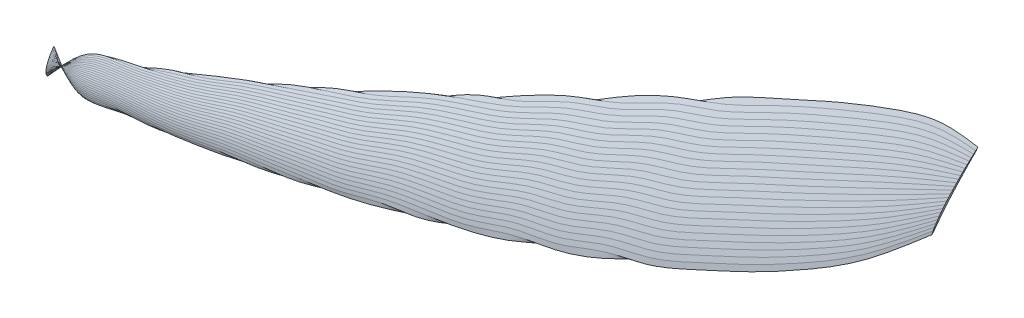
SolidWorks part; units mm, degrees
ref_plane "Front Plane" through (0, 0, 0) normal (0, 0, 1) x (1, 0, 0)
ref_plane "Top Plane" through (0, 0, 0) normal (0, 1, 0) x (1, 0, 0)
ref_plane "Right Plane" through (0, 0, 0) normal (1, 0, 0) x (0, 0, -1)
ref_plane "Plane1" through (560, 0, 0) normal (1, 0, 0) x (0, 0, -1)
sketch "Sketch1" plane through (560, 0, 0) normal (1, 0, 0) x (0, 0, -1)
  line L0 (6.3361, 23.506) -> (5.0614, 21.8132)
  line L1 (5.0614, 21.8132) -> (3.8256, 20.0917)
  line L2 (3.8256, 20.0917) -> (2.6281, 18.3434)
  line L3 (2.6281, 18.3434) -> (1.4689, 16.5695)
  line L4 (1.4689, 16.5695) -> (0.3482, 14.771)
  line L5 (0.3482, 14.771) -> (-0.734, 12.9491)
  line L6 (-0.734, 12.9491) -> (-1.777, 11.1045)
  line L7 (-1.777, 11.1045) -> (-2.7798, 9.2376)
  line L8 (-2.7798, 9.2376) -> (-3.7409, 7.3491)
  line L9 (-3.7409, 7.3491) -> (-4.6589, 5.4391)
  line L10 (-4.6589, 5.4391) -> (-5.5297, 3.5072)
  line L11 (-5.5297, 3.5072) -> (-6.3519, 1.5542)
  line L12 (-6.3519, 1.5542) -> (-7.1221, -0.4199)
  line L13 (-7.1221, -0.4199) -> (-7.8343, -2.4157)
  line L14 (-7.8343, -2.4157) -> (-8.4715, -4.4366)
  line L15 (-8.4715, -4.4366) -> (-9.0121, -6.4853)
  line L16 (-9.0121, -6.4853) -> (-9.447, -8.5591)
  line L17 (-9.447, -8.5591) -> (-9.7657, -10.6538)
  line L18 (-9.7657, -10.6538) -> (-9.9549, -12.7641)
  line L19 (-9.9549, -12.7641) -> (-9.9984, -14.8823)
  line L20 (-9.9984, -14.8823) -> (-9.8732, -16.9969)
  line L21 (-9.8732, -16.9969) -> (-9.5349, -19.0876)
  line L22 (-9.5349, -19.0876) -> (-8.9029, -21.1071)
  line L23 (-8.9029, -21.1071) -> (-7.7612, -22.8741)
  line L24 (-7.7612, -22.8741) -> (-5.8142, -23.3089)
  line L25 (-5.8142, -23.3089) -> (-4.3081, -21.8645)
  line L26 (-4.3081, -21.8645) -> (-3.3614, -19.9721)
  line L27 (-3.3614, -19.9721) -> (-2.659, -17.9734)
  line L28 (-2.659, -17.9734) -> (-2.0869, -15.9332)
  line L29 (-2.0869, -15.9332) -> (-1.5892, -13.8734)
  line L30 (-1.5892, -13.8734) -> (-1.1344, -11.8036)
  line L31 (-1.1344, -11.8036) -> (-0.7002, -9.7295)
  line L32 (-0.7002, -9.7295) -> (-0.2712, -7.6542)
  line L33 (-0.2712, -7.6542) -> (0.1651, -5.5805)
  line L34 (0.1651, -5.5805) -> (0.6108, -3.5087)
  line L35 (0.6108, -3.5087) -> (1.0479, -1.4352)
  line L36 (1.0479, -1.4352) -> (1.4801, 0.6394)
  line L37 (1.4801, 0.6394) -> (1.9114, 2.7142)
  line L38 (1.9114, 2.7142) -> (2.3454, 4.7884)
  line L39 (2.3454, 4.7884) -> (2.7846, 6.8616)
  line L40 (2.7846, 6.8616) -> (3.2309, 8.9331)
  line L41 (3.2309, 8.9331) -> (3.6858, 11.0029)
  line L42 (3.6858, 11.0029) -> (4.1498, 13.0706)
  line L43 (4.1498, 13.0706) -> (4.623, 15.1362)
  line L44 (4.623, 15.1362) -> (5.1055, 17.1997)
  line L45 (5.1055, 17.1997) -> (5.5963, 19.2612)
  line L46 (5.5963, 19.2612) -> (6.0946, 21.3209)
  line L47 (6.0946, 21.3209) -> (6.3361, 23.506)
ref_plane "Plane2" through (618.1875, 0, 0) normal (1, 0, 0) x (0, 0, -1)
sketch "Sketch2" plane through (618.1875, 0, 0) normal (1, 0, 0) x (0, 0, -1)
  line L0 (21.3816, 31.2165) -> (19.6626, 28.9786)
  line L1 (19.6626, 28.9786) -> (17.993, 26.7036)
  line L2 (17.993, 26.7036) -> (16.372, 24.3938)
  line L3 (16.372, 24.3938) -> (14.7997, 22.0505)
  line L4 (14.7997, 22.0505) -> (13.2762, 19.6752)
  line L5 (13.2762, 19.6752) -> (11.8016, 17.2692)
  line L6 (11.8016, 17.2692) -> (10.3769, 14.8334)
  line L7 (10.3769, 14.8334) -> (9.0032, 12.3684)
  line L8 (9.0032, 12.3684) -> (7.6822, 9.8748)
  line L9 (7.6822, 9.8748) -> (6.4163, 7.3528)
  line L10 (6.4163, 7.3528) -> (5.2096, 4.8019)
  line L11 (5.2096, 4.8019) -> (4.064, 2.2231)
  line L12 (4.064, 2.2231) -> (2.9836, -0.3838)
  line L13 (2.9836, -0.3838) -> (1.9767, -3.0199)
  line L14 (1.9767, -3.0199) -> (1.062, -5.6892)
  line L15 (1.062, -5.6892) -> (0.2698, -8.3974)
  line L16 (0.2698, -8.3974) -> (-0.3882, -11.1412)
  line L17 (-0.3882, -11.1412) -> (-0.8983, -13.9163)
  line L18 (-0.8983, -13.9163) -> (-1.2464, -16.7163)
  line L19 (-1.2464, -16.7163) -> (-1.4104, -19.5329)
  line L20 (-1.4104, -19.5329) -> (-1.3641, -22.3536)
  line L21 (-1.3641, -22.3536) -> (-1.0503, -25.1566)
  line L22 (-1.0503, -25.1566) -> (-0.3671, -27.891)
  line L23 (-0.3671, -27.891) -> (0.9874, -30.3437)
  line L24 (0.9874, -30.3437) -> (3.5302, -30.8718)
  line L25 (3.5302, -30.8718) -> (5.3879, -28.7926)
  line L26 (5.3879, -28.7926) -> (6.5789, -26.2374)
  line L27 (6.5789, -26.2374) -> (7.4965, -23.5694)
  line L28 (7.4965, -23.5694) -> (8.2758, -20.8574)
  line L29 (8.2758, -20.8574) -> (8.9785, -18.1244)
  line L30 (8.9785, -18.1244) -> (9.6413, -15.3814)
  line L31 (9.6413, -15.3814) -> (10.2893, -12.6348)
  line L32 (10.2893, -12.6348) -> (10.9409, -9.8891)
  line L33 (10.9409, -9.8891) -> (11.6102, -7.1477)
  line L34 (11.6102, -7.1477) -> (12.2955, -4.4102)
  line L35 (12.2955, -4.4102) -> (12.9735, -1.6709)
  line L36 (12.9735, -1.6709) -> (13.6491, 1.069)
  line L37 (13.6491, 1.069) -> (14.3273, 3.8082)
  line L38 (14.3273, 3.8082) -> (15.012, 6.5458)
  line L39 (15.012, 6.5458) -> (15.7062, 9.2811)
  line L40 (15.7062, 9.2811) -> (16.4121, 12.0133)
  line L41 (16.4121, 12.0133) -> (17.1313, 14.7421)
  line L42 (17.1313, 14.7421) -> (17.8645, 17.4671)
  line L43 (17.8645, 17.4671) -> (18.6117, 20.1884)
  line L44 (18.6117, 20.1884) -> (19.3729, 22.9057)
  line L45 (19.3729, 22.9057) -> (20.147, 25.6194)
  line L46 (20.147, 25.6194) -> (20.9328, 28.3297)
  line L47 (20.9328, 28.3297) -> (21.3816, 31.2165)
ref_plane "Plane3" through (676.375, 0, 0) normal (1, 0, 0) x (0, 0, -1)
sketch "Sketch3" plane through (676.375, 0, 0) normal (1, 0, 0) x (0, 0, -1)
  line L0 (39.403, 37.0958) -> (37.3256, 34.4466)
  line L1 (37.3256, 34.4466) -> (35.3042, 31.7544)
  line L2 (35.3042, 31.7544) -> (33.338, 29.0216)
  line L3 (33.338, 29.0216) -> (31.4273, 26.2498)
  line L4 (31.4273, 26.2498) -> (29.5721, 23.4405)
  line L5 (29.5721, 23.4405) -> (27.7727, 20.5951)
  line L6 (27.7727, 20.5951) -> (26.03, 17.7146)
  line L7 (26.03, 17.7146) -> (24.3455, 14.7998)
  line L8 (24.3455, 14.7998) -> (22.7207, 11.8512)
  line L9 (22.7207, 11.8512) -> (21.1588, 8.8689)
  line L10 (21.1588, 8.8689) -> (19.6636, 5.8526)
  line L11 (19.6636, 5.8526) -> (18.2372, 2.8031)
  line L12 (18.2372, 2.8031) -> (16.8846, -0.2798)
  line L13 (16.8846, -0.2798) -> (15.6143, -3.3975)
  line L14 (15.6143, -3.3975) -> (14.4464, -6.5548)
  line L15 (14.4464, -6.5548) -> (13.4177, -9.7601)
  line L16 (13.4177, -9.7601) -> (12.5427, -13.0107)
  line L17 (12.5427, -13.0107) -> (11.8349, -16.3017)
  line L18 (11.8349, -16.3017) -> (11.3086, -19.6265)
  line L19 (11.3086, -19.6265) -> (10.991, -22.9775)
  line L20 (10.991, -22.9775) -> (10.9083, -26.3423)
  line L21 (10.9083, -26.3423) -> (11.1251, -29.7006)
  line L22 (11.1251, -29.7006) -> (11.7565, -33.0038)
  line L23 (11.7565, -33.0038) -> (13.1712, -36.0333)
  line L24 (13.1712, -36.0333) -> (16.1307, -36.5557)
  line L25 (16.1307, -36.5557) -> (18.1767, -33.9182)
  line L26 (18.1767, -33.9182) -> (19.5316, -30.8386)
  line L27 (19.5316, -30.8386) -> (20.6226, -27.6542)
  line L28 (20.6226, -27.6542) -> (21.5811, -24.4269)
  line L29 (21.5811, -24.4269) -> (22.4714, -21.1801)
  line L30 (22.4714, -21.1801) -> (23.3324, -17.9255)
  line L31 (23.3324, -17.9255) -> (24.1895, -14.6697)
  line L32 (24.1895, -14.6697) -> (25.0615, -11.418)
  line L33 (25.0615, -11.418) -> (25.9631, -8.1743)
  line L34 (25.9631, -8.1743) -> (26.8866, -4.9368)
  line L35 (26.8866, -4.9368) -> (27.8065, -1.6982)
  line L36 (27.8065, -1.6982) -> (28.7282, 1.5398)
  line L37 (28.7282, 1.5398) -> (29.6568, 4.7759)
  line L38 (29.6568, 4.7759) -> (30.5964, 8.0088)
  line L39 (30.5964, 8.0088) -> (31.55, 11.2375)
  line L40 (31.55, 11.2375) -> (32.5201, 14.4614)
  line L41 (32.5201, 14.4614) -> (33.508, 17.6798)
  line L42 (33.508, 17.6798) -> (34.5146, 20.8925)
  line L43 (34.5146, 20.8925) -> (35.5398, 24.0993)
  line L44 (35.5398, 24.0993) -> (36.5836, 27.3)
  line L45 (36.5836, 27.3) -> (37.6447, 30.4951)
  line L46 (37.6447, 30.4951) -> (38.7218, 33.6848)
  line L47 (38.7218, 33.6848) -> (39.403, 37.0958)
ref_plane "Plane4" through (734.5625, 0, 0) normal (1, 0, 0) x (0, 0, -1)
sketch "Sketch4" plane through (734.5625, 0, 0) normal (1, 0, 0) x (0, 0, -1)
  line L0 (60.5598, 42.9415) -> (58.1177, 39.8798)
  line L1 (58.1177, 39.8798) -> (55.7372, 36.7699)
  line L2 (55.7372, 36.7699) -> (53.4174, 33.6144)
  line L3 (53.4174, 33.6144) -> (51.1589, 30.4148)
  line L4 (51.1589, 30.4148) -> (48.9615, 27.173)
  line L5 (48.9615, 27.173) -> (46.8257, 23.8902)
  line L6 (46.8257, 23.8902) -> (44.7523, 20.5676)
  line L7 (44.7523, 20.5676) -> (42.743, 17.206)
  line L8 (42.743, 17.206) -> (40.7994, 13.8059)
  line L9 (40.7994, 13.8059) -> (38.9251, 10.3671)
  line L10 (38.9251, 10.3671) -> (37.1235, 6.8897)
  line L11 (37.1235, 6.8897) -> (35.3971, 3.3744)
  line L12 (35.3971, 3.3744) -> (33.7517, -0.1795)
  line L13 (33.7517, -0.1795) -> (32.1952, -3.7733)
  line L14 (32.1952, -3.7733) -> (30.7491, -7.4127)
  line L15 (30.7491, -7.4127) -> (29.4561, -11.1092)
  line L16 (29.4561, -11.1092) -> (28.3334, -14.861)
  line L17 (28.3334, -14.861) -> (27.3933, -18.6625)
  line L18 (27.3933, -18.6625) -> (26.652, -22.5077)
  line L19 (26.652, -22.5077) -> (26.1376, -26.3895)
  line L20 (26.1376, -26.3895) -> (25.8803, -30.2967)
  line L21 (25.8803, -30.2967) -> (25.9467, -34.2111)
  line L22 (25.9467, -34.2111) -> (26.4661, -38.0894)
  line L23 (26.4661, -38.0894) -> (27.8743, -41.716)
  line L24 (27.8743, -41.716) -> (31.2137, -42.1175)
  line L25 (31.2137, -42.1175) -> (33.4163, -38.9059)
  line L26 (33.4163, -38.9059) -> (34.9516, -35.3049)
  line L27 (34.9516, -35.3049) -> (36.2355, -31.6052)
  line L28 (36.2355, -31.6052) -> (37.4011, -27.8662)
  line L29 (37.4011, -27.8662) -> (38.5109, -24.1103)
  line L30 (38.5109, -24.1103) -> (39.6023, -20.349)
  line L31 (39.6023, -20.349) -> (40.7017, -16.59)
  line L32 (40.7017, -16.59) -> (41.8278, -12.8389)
  line L33 (41.8278, -12.8389) -> (42.995, -9.1005)
  line L34 (42.995, -9.1005) -> (44.1892, -5.3705)
  line L35 (44.1892, -5.3705) -> (45.384, -1.6407)
  line L36 (45.384, -1.6407) -> (46.5848, 2.0871)
  line L37 (46.5848, 2.0871) -> (47.7971, 5.8112)
  line L38 (47.7971, 5.8112) -> (49.0249, 9.5303)
  line L39 (49.0249, 9.5303) -> (50.2711, 13.2432)
  line L40 (50.2711, 13.2432) -> (51.5383, 16.949)
  line L41 (51.5383, 16.949) -> (52.8278, 20.6471)
  line L42 (52.8278, 20.6471) -> (54.1404, 24.337)
  line L43 (54.1404, 24.337) -> (55.4759, 28.0188)
  line L44 (55.4759, 28.0188) -> (56.8343, 31.6921)
  line L45 (56.8343, 31.6921) -> (58.2143, 35.3574)
  line L46 (58.2143, 35.3574) -> (59.6142, 39.0151)
  line L47 (59.6142, 39.0151) -> (60.5598, 42.9415)
ref_plane "Plane5" through (792.75, 0, 0) normal (1, 0, 0) x (0, 0, -1)
sketch "Sketch5" plane through (792.75, 0, 0) normal (1, 0, 0) x (0, 0, -1)
  line L0 (84.7982, 49.1414) -> (81.961, 45.6375)
  line L1 (81.961, 45.6375) -> (79.1907, 42.0805)
  line L2 (79.1907, 42.0805) -> (76.4862, 38.4732)
  line L3 (76.4862, 38.4732) -> (73.8483, 34.8169)
  line L4 (73.8483, 34.8169) -> (71.2765, 31.1138)
  line L5 (71.2765, 31.1138) -> (68.7718, 27.365)
  line L6 (68.7718, 27.365) -> (66.3347, 23.5719)
  line L7 (66.3347, 23.5719) -> (63.967, 19.7352)
  line L8 (63.967, 19.7352) -> (61.6704, 15.8554)
  line L9 (61.6704, 15.8554) -> (59.449, 11.9321)
  line L10 (59.449, 11.9321) -> (57.3057, 7.9656)
  line L11 (57.3057, 7.9656) -> (55.2433, 3.9565)
  line L12 (55.2433, 3.9565) -> (53.2683, -0.0964)
  line L13 (53.2683, -0.0964) -> (51.3881, -4.1941)
  line L14 (51.3881, -4.1941) -> (49.6251, -8.3434)
  line L15 (49.6251, -8.3434) -> (48.0277, -12.5592)
  line L16 (48.0277, -12.5592) -> (46.6159, -16.8407)
  line L17 (46.6159, -16.8407) -> (45.4005, -21.1819)
  line L18 (45.4005, -21.1819) -> (44.3994, -25.5775)
  line L19 (44.3994, -25.5775) -> (43.6416, -30.0213)
  line L20 (43.6416, -30.0213) -> (43.1604, -34.5032)
  line L21 (43.1604, -34.5032) -> (43.0249, -39.0084)
  line L22 (43.0249, -39.0084) -> (43.3769, -43.4996)
  line L23 (43.3769, -43.4996) -> (44.7206, -47.7733)
  line L24 (44.7206, -47.7733) -> (48.4276, -47.9326)
  line L25 (48.4276, -47.9326) -> (50.8033, -44.1197)
  line L26 (50.8033, -44.1197) -> (52.5527, -39.9658)
  line L27 (52.5527, -39.9658) -> (54.0719, -35.7211)
  line L28 (54.0719, -35.7211) -> (55.4855, -31.4399)
  line L29 (55.4855, -31.4399) -> (56.8566, -27.1448)
  line L30 (56.8566, -27.1448) -> (58.2222, -22.848)
  line L31 (58.2222, -22.848) -> (59.6076, -18.5575)
  line L32 (59.6076, -18.5575) -> (61.0315, -14.2797)
  line L33 (61.0315, -14.2797) -> (62.508, -10.0198)
  line L34 (62.508, -10.0198) -> (64.0161, -5.7708)
  line L35 (64.0161, -5.7708) -> (65.5289, -1.5236)
  line L36 (65.5289, -1.5236) -> (67.0522, 2.7199)
  line L37 (67.0522, 2.7199) -> (68.5917, 6.9575)
  line L38 (68.5917, 6.9575) -> (70.1511, 11.1879)
  line L39 (70.1511, 11.1879) -> (71.7334, 15.4097)
  line L40 (71.7334, 15.4097) -> (73.341, 19.6219)
  line L41 (73.341, 19.6219) -> (74.9753, 23.8239)
  line L42 (74.9753, 23.8239) -> (76.637, 28.0151)
  line L43 (76.637, 28.0151) -> (78.3259, 32.1954)
  line L44 (78.3259, 32.1954) -> (80.0419, 36.3647)
  line L45 (80.0419, 36.3647) -> (81.7836, 40.5233)
  line L46 (81.7836, 40.5233) -> (83.5493, 44.6718)
  line L47 (83.5493, 44.6718) -> (84.7982, 49.1414)
ref_plane "Plane6" through (850.9375, 0, 0) normal (1, 0, 0) x (0, 0, -1)
sketch "Sketch6" plane through (850.9375, 0, 0) normal (1, 0, 0) x (0, 0, -1)
  line L0 (111.9093, 55.4384) -> (108.6555, 51.483)
  line L1 (108.6555, 51.483) -> (105.4732, 47.4699)
  line L2 (105.4732, 47.4699) -> (102.3613, 43.402)
  line L3 (102.3613, 43.402) -> (99.3207, 39.2804)
  line L4 (99.3207, 39.2804) -> (96.3509, 35.1076)
  line L5 (96.3509, 35.1076) -> (93.4528, 30.8846)
  line L6 (93.4528, 30.8846) -> (90.6272, 26.6129)
  line L7 (90.6272, 26.6129) -> (87.8756, 22.293)
  line L8 (87.8756, 22.293) -> (85.2, 17.9258)
  line L9 (85.2, 17.9258) -> (82.6048, 13.5102)
  line L10 (82.6048, 13.5102) -> (80.0923, 9.0471)
  line L11 (80.0923, 9.0471) -> (77.6657, 4.5367)
  line L12 (77.6657, 4.5367) -> (75.332, -0.0224)
  line L13 (75.332, -0.0224) -> (73.0979, -4.6312)
  line L14 (73.0979, -4.6312) -> (70.9869, -9.2973)
  line L15 (70.9869, -9.2973) -> (69.0528, -14.0396)
  line L16 (69.0528, -14.0396) -> (67.3172, -18.858)
  line L17 (67.3172, -18.858) -> (65.7902, -23.7464)
  line L18 (65.7902, -23.7464) -> (64.491, -28.7001)
  line L19 (64.491, -28.7001) -> (63.4488, -33.7141)
  line L20 (63.4488, -33.7141) -> (62.6993, -38.7798)
  line L21 (62.6993, -38.7798) -> (62.3132, -43.8857)
  line L22 (62.3132, -43.8857) -> (62.4417, -49.0023)
  line L23 (62.4417, -49.0023) -> (63.6555, -53.9454)
  line L24 (63.6555, -53.9454) -> (67.688, -53.7533)
  line L25 (67.688, -53.7533) -> (70.2552, -49.3348)
  line L26 (70.2552, -49.3348) -> (72.2442, -44.6159)
  line L27 (72.2442, -44.6159) -> (74.0262, -39.8143)
  line L28 (74.0262, -39.8143) -> (75.7213, -34.9811)
  line L29 (75.7213, -34.9811) -> (77.3881, -30.1381)
  line L30 (77.3881, -30.1381) -> (79.0628, -25.2978)
  line L31 (79.0628, -25.2978) -> (80.7701, -20.469)
  line L32 (80.7701, -20.469) -> (82.5285, -15.6585)
  line L33 (82.5285, -15.6585) -> (84.3514, -10.8721)
  line L34 (84.3514, -10.8721) -> (86.2103, -6.0996)
  line L35 (86.2103, -6.0996) -> (88.0788, -1.3307)
  line L36 (88.0788, -1.3307) -> (89.9626, 3.432)
  line L37 (89.9626, 3.432) -> (91.8674, 8.1865)
  line L38 (91.8674, 8.1865) -> (93.797, 12.9309)
  line L39 (93.797, 12.9309) -> (95.7541, 17.664)
  line L40 (95.7541, 17.664) -> (97.741, 22.3847)
  line L41 (97.741, 22.3847) -> (99.7592, 27.0921)
  line L42 (99.7592, 27.0921) -> (101.8092, 31.7858)
  line L43 (101.8092, 31.7858) -> (103.8908, 36.4655)
  line L44 (103.8908, 36.4655) -> (106.0038, 41.1311)
  line L45 (106.0038, 41.1311) -> (108.1468, 45.7831)
  line L46 (108.1468, 45.7831) -> (110.3179, 50.4219)
  line L47 (110.3179, 50.4219) -> (111.9093, 55.4384)
ref_plane "Plane7" through (909.125, 0, 0) normal (1, 0, 0) x (0, 0, -1)
sketch "Sketch7" plane through (909.125, 0, 0) normal (1, 0, 0) x (0, 0, -1)
  line L0 (141.8104, 61.8077) -> (138.1179, 57.3929)
  line L1 (138.1179, 57.3929) -> (134.5011, 52.916)
  line L2 (134.5011, 52.916) -> (130.9586, 48.3799)
  line L3 (130.9586, 48.3799) -> (127.4916, 43.7858)
  line L4 (127.4916, 43.7858) -> (124.0995, 39.1363)
  line L5 (124.0995, 39.1363) -> (120.7834, 34.4322)
  line L6 (120.7834, 34.4322) -> (117.5439, 29.675)
  line L7 (117.5439, 29.675) -> (114.3826, 24.8655)
  line L8 (114.3826, 24.8655) -> (111.3015, 20.0043)
  line L9 (111.3015, 20.0043) -> (108.3054, 15.0902)
  line L10 (108.3054, 15.0902) -> (105.3961, 10.1242)
  line L11 (105.3961, 10.1242) -> (102.5768, 5.1066)
  line L12 (102.5768, 5.1066) -> (99.8553, 0.0354)
  line L13 (99.8553, 0.0354) -> (97.2372, -5.0901)
  line L14 (97.2372, -5.0901) -> (94.7468, -10.2785)
  line L15 (94.7468, -10.2785) -> (92.444, -15.5529)
  line L16 (92.444, -15.5529) -> (90.3498, -20.9135)
  line L17 (90.3498, -20.9135) -> (88.4751, -26.3546)
  line L18 (88.4751, -26.3546) -> (86.8395, -31.8722)
  line L19 (86.8395, -31.8722) -> (85.4723, -37.4623)
  line L20 (85.4723, -37.4623) -> (84.4108, -43.1182)
  line L21 (84.4108, -43.1182) -> (83.726, -48.8314)
  line L22 (83.726, -48.8314) -> (83.5754, -54.5815)
  line L23 (83.5754, -54.5815) -> (84.5911, -60.2113)
  line L24 (84.5911, -60.2113) -> (88.9125, -59.5634)
  line L25 (88.9125, -59.5634) -> (91.692, -54.5332)
  line L26 (91.692, -54.5332) -> (93.9519, -49.2407)
  line L27 (93.9519, -49.2407) -> (96.0304, -43.8737)
  line L28 (96.0304, -43.8737) -> (98.0399, -38.4804)
  line L29 (98.0399, -38.4804) -> (100.037, -33.0825)
  line L30 (100.037, -33.0825) -> (102.0562, -27.6929)
  line L31 (102.0562, -27.6929) -> (104.1218, -22.3208)
  line L32 (104.1218, -22.3208) -> (106.2507, -16.9736)
  line L33 (106.2507, -16.9736) -> (108.4564, -11.6575)
  line L34 (108.4564, -11.6575) -> (110.7028, -6.3585)
  line L35 (110.7028, -6.3585) -> (112.9639, -1.0658)
  line L36 (112.9639, -1.0658) -> (115.2456, 4.2181)
  line L37 (115.2456, 4.2181) -> (117.5531, 9.4908)
  line L38 (117.5531, 9.4908) -> (119.8905, 14.7503)
  line L39 (119.8905, 14.7503) -> (122.2602, 19.9953)
  line L40 (122.2602, 19.9953) -> (124.6643, 25.2246)
  line L41 (124.6643, 25.2246) -> (127.1043, 30.4373)
  line L42 (127.1043, 30.4373) -> (129.5805, 35.6329)
  line L43 (129.5805, 35.6329) -> (132.0929, 40.8111)
  line L44 (132.0929, 40.8111) -> (134.6411, 45.9717)
  line L45 (134.6411, 45.9717) -> (137.2236, 51.1153)
  line L46 (137.2236, 51.1153) -> (139.8386, 56.2424)
  line L47 (139.8386, 56.2424) -> (141.8104, 61.8077)
ref_plane "Plane8" through (967.3125, 0, 0) normal (1, 0, 0) x (0, 0, -1)
sketch "Sketch8" plane through (967.3125, 0, 0) normal (1, 0, 0) x (0, 0, -1)
  line L0 (174.4315, 68.2102) -> (170.2788, 63.3304)
  line L1 (170.2788, 63.3304) -> (166.2053, 58.3844)
  line L2 (166.2053, 58.3844) -> (162.2096, 53.3753)
  line L3 (162.2096, 53.3753) -> (158.2932, 48.3039)
  line L4 (158.2932, 48.3039) -> (154.4551, 43.173)
  line L5 (154.4551, 43.173) -> (150.6967, 37.9834)
  line L6 (150.6967, 37.9834) -> (147.0186, 32.7367)
  line L7 (147.0186, 32.7367) -> (143.4224, 27.4335)
  line L8 (143.4224, 27.4335) -> (139.9099, 22.0744)
  line L9 (139.9099, 22.0744) -> (136.4864, 16.6581)
  line L10 (136.4864, 16.6581) -> (133.1531, 11.1858)
  line L11 (133.1531, 11.1858) -> (129.9134, 5.6576)
  line L12 (129.9134, 5.6576) -> (126.7753, 0.0711)
  line L13 (126.7753, 0.0711) -> (123.7438, -5.5739)
  line L14 (123.7438, -5.5739) -> (120.8436, -11.2873)
  line L15 (120.8436, -11.2873) -> (118.1401, -17.0963)
  line L16 (118.1401, -17.0963) -> (115.6538, -23.0015)
  line L17 (115.6538, -23.0015) -> (113.3962, -28.9977)
  line L18 (113.3962, -28.9977) -> (111.387, -35.0817)
  line L19 (111.387, -35.0817) -> (109.6552, -41.2501)
  line L20 (109.6552, -41.2501) -> (108.2387, -47.4984)
  line L21 (108.2387, -47.4984) -> (107.2084, -53.8214)
  line L22 (107.2084, -53.8214) -> (106.7249, -60.2075)
  line L23 (106.7249, -60.2075) -> (107.47, -66.5348)
  line L24 (107.47, -66.5348) -> (112.0557, -65.3352)
  line L25 (112.0557, -65.3352) -> (115.079, -59.6921)
  line L26 (115.079, -59.6921) -> (117.639, -53.8186)
  line L27 (117.639, -53.8186) -> (120.0457, -47.8801)
  line L28 (120.0457, -47.8801) -> (122.403, -41.9219)
  line L29 (122.403, -41.9219) -> (124.7646, -35.9653)
  line L30 (124.7646, -35.9653) -> (127.164, -30.0239)
  line L31 (127.164, -30.0239) -> (129.6231, -24.1069)
  line L32 (129.6231, -24.1069) -> (132.158, -18.2221)
  line L33 (132.158, -18.2221) -> (134.7805, -12.3758)
  line L34 (134.7805, -12.3758) -> (137.4496, -6.5505)
  line L35 (137.4496, -6.5505) -> (140.1389, -0.7345)
  line L36 (140.1389, -0.7345) -> (142.854, 5.0694)
  line L37 (142.854, 5.0694) -> (145.5999, 10.8589)
  line L38 (145.5999, 10.8589) -> (148.381, 16.6315)
  line L39 (148.381, 16.6315) -> (151.1992, 22.3861)
  line L40 (151.1992, 22.3861) -> (154.0564, 28.1214)
  line L41 (154.0564, 28.1214) -> (156.9541, 33.8364)
  line L42 (156.9541, 33.8364) -> (159.8925, 39.5306)
  line L43 (159.8925, 39.5306) -> (162.8716, 45.2036)
  line L44 (162.8716, 45.2036) -> (165.8907, 50.8553)
  line L45 (165.8907, 50.8553) -> (168.9487, 56.4862)
  line L46 (168.9487, 56.4862) -> (172.0434, 62.0969)
  line L47 (172.0434, 62.0969) -> (174.4315, 68.2102)
ref_plane "Plane9" through (1025.5, 0, 0) normal (1, 0, 0) x (0, 0, -1)
sketch "Sketch9" plane through (1025.5, 0, 0) normal (1, 0, 0) x (0, 0, -1)
  line L0 (209.7049, 74.6134) -> (205.0705, 69.2656)
  line L1 (205.0705, 69.2656) -> (200.5183, 63.8477)
  line L2 (200.5183, 63.8477) -> (196.047, 58.3628)
  line L3 (196.047, 58.3628) -> (191.6582, 52.8117)
  line L4 (191.6582, 52.8117) -> (187.3507, 47.1972)
  line L5 (187.3507, 47.1972) -> (183.1262, 41.5201)
  line L6 (183.1262, 41.5201) -> (178.985, 35.7818)
  line L7 (178.985, 35.7818) -> (174.929, 29.9831)
  line L8 (174.929, 29.9831) -> (170.9597, 24.1247)
  line L9 (170.9597, 24.1247) -> (167.0829, 18.2047)
  line L10 (167.0829, 18.2047) -> (163.299, 12.2248)
  line L11 (163.299, 12.2248) -> (159.6116, 6.185)
  line L12 (159.6116, 6.185) -> (156.0291, 0.0824)
  line L13 (156.0291, 0.0824) -> (152.5555, -6.0828)
  line L14 (152.5555, -6.0828) -> (149.2162, -12.3216)
  line L15 (149.2162, -12.3216) -> (146.0812, -18.6655)
  line L16 (146.0812, -18.6655) -> (143.1706, -25.1153)
  line L17 (143.1706, -25.1153) -> (140.4964, -31.6666)
  line L18 (140.4964, -31.6666) -> (138.078, -38.3165)
  line L19 (138.078, -38.3165) -> (135.9438, -45.0629)
  line L20 (135.9438, -45.0629) -> (134.1319, -51.9027)
  line L21 (134.1319, -51.9027) -> (132.7123, -58.8342)
  line L22 (132.7123, -58.8342) -> (131.8459, -65.8544)
  line L23 (131.8459, -65.8544) -> (132.2512, -72.8823)
  line L24 (132.2512, -72.8823) -> (137.0887, -71.0517)
  line L25 (137.0887, -71.0517) -> (140.3873, -64.7955)
  line L26 (140.3873, -64.7955) -> (143.2829, -58.3389)
  line L27 (143.2829, -58.3389) -> (146.0514, -51.8263)
  line L28 (146.0514, -51.8263) -> (148.7907, -45.3015)
  line L29 (148.7907, -45.3015) -> (151.5513, -38.7856)
  line L30 (151.5513, -38.7856) -> (154.3641, -32.2922)
  line L31 (154.3641, -32.2922) -> (157.2502, -25.8309)
  line L32 (157.2502, -25.8309) -> (160.2248, -19.41)
  line L33 (160.2248, -19.41) -> (163.2974, -13.0354)
  line L34 (163.2974, -13.0354) -> (166.422, -6.686)
  line L35 (166.422, -6.686) -> (169.5726, -0.3496)
  line L36 (169.5726, -0.3496) -> (172.7544, 5.9713)
  line L37 (172.7544, 5.9713) -> (175.9719, 12.2741)
  line L38 (175.9719, 12.2741) -> (179.2297, 18.5561)
  line L39 (179.2297, 18.5561) -> (182.5294, 24.8163)
  line L40 (182.5294, 24.8163) -> (185.8727, 31.0532)
  line L41 (185.8727, 31.0532) -> (189.2609, 37.2659)
  line L42 (189.2609, 37.2659) -> (192.6943, 43.4538)
  line L43 (192.6943, 43.4538) -> (196.1726, 49.6164)
  line L44 (196.1726, 49.6164) -> (199.6953, 55.7538)
  line L45 (199.6953, 55.7538) -> (203.2612, 61.8662)
  line L46 (203.2612, 61.8662) -> (206.8681, 67.9546)
  line L47 (206.8681, 67.9546) -> (209.7049, 74.6134)
ref_plane "Plane10" through (1083.6875, 0, 0) normal (1, 0, 0) x (0, 0, -1)
sketch "Sketch10" plane through (1083.6875, 0, 0) normal (1, 0, 0) x (0, 0, -1)
  line L0 (247.5506, 80.9439) -> (242.4162, 75.1302)
  line L1 (242.4162, 75.1302) -> (237.3666, 69.2427)
  line L2 (237.3666, 69.2427) -> (232.4004, 63.2847)
  line L3 (232.4004, 63.2847) -> (227.5193, 57.2568)
  line L4 (227.5193, 57.2568) -> (222.7221, 51.1619)
  line L5 (222.7221, 51.1619) -> (218.0105, 45.0006)
  line L6 (218.0105, 45.0006) -> (213.385, 38.7744)
  line L7 (213.385, 38.7744) -> (208.8472, 32.484)
  line L8 (208.8472, 32.484) -> (204.3988, 26.13)
  line L9 (204.3988, 26.13) -> (200.0454, 19.7106)
  line L10 (200.0454, 19.7106) -> (195.7873, 13.2276)
  line L11 (195.7873, 13.2276) -> (191.6279, 6.6808)
  line L12 (191.6279, 6.6808) -> (187.576, 0.067)
  line L13 (187.576, 0.067) -> (183.6347, -6.6133)
  line L14 (183.6347, -6.6133) -> (179.8296, -13.3719)
  line L15 (179.8296, -13.3719) -> (176.2352, -20.2448)
  line L16 (176.2352, -20.2448) -> (172.871, -27.2332)
  line L17 (172.871, -27.2332) -> (169.7491, -34.3331)
  line L18 (169.7491, -34.3331) -> (166.8886, -41.5422)
  line L19 (166.8886, -41.5422) -> (164.3171, -48.8593)
  line L20 (164.3171, -48.8593) -> (162.0723, -56.283)
  line L21 (162.0723, -56.283) -> (160.2225, -63.8144)
  line L22 (160.2225, -63.8144) -> (158.9263, -71.4589)
  line L23 (158.9263, -71.4589) -> (158.9321, -79.1775)
  line L24 (158.9321, -79.1775) -> (164.008, -76.6529)
  line L25 (164.008, -76.6529) -> (167.62, -69.7921)
  line L26 (167.62, -69.7921) -> (170.8814, -62.7549)
  line L27 (170.8814, -62.7549) -> (174.0436, -55.6724)
  line L28 (174.0436, -55.6724) -> (177.1963, -48.5856)
  line L29 (177.1963, -48.5856) -> (180.3872, -41.516)
  line L30 (180.3872, -41.516) -> (183.6445, -34.4767)
  line L31 (183.6445, -34.4767) -> (186.9883, -27.4781)
  line L32 (186.9883, -27.4781) -> (190.4327, -20.5285)
  line L33 (190.4327, -20.5285) -> (193.9852, -13.6336)
  line L34 (193.9852, -13.6336) -> (197.5947, -6.7682)
  line L35 (197.5947, -6.7682) -> (201.2361, 0.0803)
  line L36 (201.2361, 0.0803) -> (204.9141, 6.9092)
  line L37 (204.9141, 6.9092) -> (208.6326, 13.7162)
  line L38 (208.6326, 13.7162) -> (212.3961, 20.4984)
  line L39 (212.3961, 20.4984) -> (216.2062, 27.2545)
  line L40 (216.2062, 27.2545) -> (220.0643, 33.9832)
  line L41 (220.0643, 33.9832) -> (223.9716, 40.6836)
  line L42 (223.9716, 40.6836) -> (227.9282, 47.355)
  line L43 (227.9282, 47.355) -> (231.934, 53.9969)
  line L44 (231.934, 53.9969) -> (235.9882, 60.6094)
  line L45 (235.9882, 60.6094) -> (240.0899, 67.1925)
  line L46 (240.0899, 67.1925) -> (244.2365, 73.7475)
  line L47 (244.2365, 73.7475) -> (247.5506, 80.9439)
ref_plane "Plane11" through (1141.875, 0, 0) normal (1, 0, 0) x (0, 0, -1)
sketch "Sketch11" plane through (1141.875, 0, 0) normal (1, 0, 0) x (0, 0, -1)
  line L0 (287.8931, 87.1216) -> (282.2447, 80.8498)
  line L1 (282.2447, 80.8498) -> (276.6829, 74.501)
  line L2 (276.6829, 74.501) -> (271.2065, 68.0784)
  line L3 (271.2065, 68.0784) -> (265.8173, 61.5824)
  line L4 (265.8173, 61.5824) -> (260.5141, 55.0161)
  line L5 (260.5141, 55.0161) -> (255.2986, 48.3799)
  line L6 (255.2986, 48.3799) -> (250.1712, 41.6754)
  line L7 (250.1712, 41.6754) -> (245.1336, 34.9031)
  line L8 (245.1336, 34.9031) -> (240.1875, 28.0638)
  line L9 (240.1875, 28.0638) -> (235.3383, 21.1554)
  line L10 (235.3383, 21.1554) -> (230.5862, 14.1799)
  line L11 (230.5862, 14.1799) -> (225.9344, 7.1371)
  line L12 (225.9344, 7.1371) -> (221.3917, 0.0234)
  line L13 (221.3917, 0.0234) -> (216.9607, -7.1604)
  line L14 (216.9607, -7.1604) -> (212.667, -14.4268)
  line L15 (212.667, -14.4268) -> (208.5889, -21.8164)
  line L16 (208.5889, -21.8164) -> (204.7452, -29.3305)
  line L17 (204.7452, -29.3305) -> (201.1482, -36.9656)
  line L18 (201.1482, -36.9656) -> (197.8161, -44.72)
  line L19 (197.8161, -44.72) -> (194.7759, -52.5933)
  line L20 (194.7759, -52.5933) -> (192.0639, -60.5855)
  line L21 (192.0639, -60.5855) -> (189.7464, -68.7005)
  line L22 (189.7464, -68.7005) -> (187.9776, -76.9509)
  line L23 (187.9776, -76.9509) -> (187.5259, -85.3407)
  line L24 (187.5259, -85.3407) -> (192.8391, -82.0754)
  line L25 (192.8391, -82.0754) -> (196.7955, -74.6218)
  line L26 (196.7955, -74.6218) -> (200.4515, -67.0143)
  line L27 (200.4515, -67.0143) -> (204.0361, -59.3728)
  line L28 (204.0361, -59.3728) -> (207.6309, -51.7361)
  line L29 (207.6309, -51.7361) -> (211.2798, -44.1252)
  line L30 (211.2798, -44.1252) -> (215.0091, -36.5533)
  line L31 (215.0091, -36.5533) -> (218.8374, -29.031)
  line L32 (218.8374, -29.031) -> (222.7778, -21.5669)
  line L33 (222.7778, -21.5669) -> (226.8357, -14.166)
  line L34 (226.8357, -14.166) -> (230.9554, -6.7991)
  line L35 (230.9554, -6.7991) -> (235.1128, 0.5464)
  line L36 (235.1128, 0.5464) -> (239.3118, 7.8683)
  line L37 (239.3118, 7.8683) -> (243.556, 15.1641)
  line L38 (243.556, 15.1641) -> (247.8496, 22.4309)
  line L39 (247.8496, 22.4309) -> (252.1943, 29.6673)
  line L40 (252.1943, 29.6673) -> (256.5911, 36.8721)
  line L41 (256.5911, 36.8721) -> (261.0411, 44.0442)
  line L42 (261.0411, 44.0442) -> (265.5443, 51.183)
  line L43 (265.5443, 51.183) -> (270.1007, 58.288)
  line L44 (270.1007, 58.288) -> (274.7093, 65.3592)
  line L45 (274.7093, 65.3592) -> (279.3693, 72.3967)
  line L46 (279.3693, 72.3967) -> (284.0781, 79.4017)
  line L47 (284.0781, 79.4017) -> (287.8931, 87.1216)
ref_plane "Plane12" through (1200.0625, 0, 0) normal (1, 0, 0) x (0, 0, -1)
sketch "Sketch12" plane through (1200.0625, 0, 0) normal (1, 0, 0) x (0, 0, -1)
  line L0 (330.6317, 93.0526) -> (324.4603, 86.338)
  line L1 (324.4603, 86.338) -> (318.377, 79.5435)
  line L2 (318.377, 79.5435) -> (312.3806, 72.6723)
  line L3 (312.3806, 72.6723) -> (306.4728, 65.7246)
  line L4 (306.4728, 65.7246) -> (300.6525, 58.7035)
  line L5 (300.6525, 58.7035) -> (294.9216, 51.6093)
  line L6 (294.9216, 51.6093) -> (289.2803, 44.4435)
  line L7 (289.2803, 44.4435) -> (283.7302, 37.207)
  line L8 (283.7302, 37.207) -> (278.2733, 29.8999)
  line L9 (278.2733, 29.8999) -> (272.9144, 22.5206)
  line L10 (272.9144, 22.5206) -> (267.6538, 15.071)
  line L11 (267.6538, 15.071) -> (262.4945, 7.5508)
  line L12 (262.4945, 7.5508) -> (257.4455, -0.0439)
  line L13 (257.4455, -0.0439) -> (252.5084, -7.7117)
  line L14 (252.5084, -7.7117) -> (247.7091, -15.4664)
  line L15 (247.7091, -15.4664) -> (243.1288, -23.3523)
  line L16 (243.1288, -23.3523) -> (238.7858, -31.3712)
  line L17 (238.7858, -31.3712) -> (234.692, -39.5202)
  line L18 (234.692, -39.5202) -> (230.8652, -47.7979)
  line L19 (230.8652, -47.7979) -> (227.3312, -56.2046)
  line L20 (227.3312, -56.2046) -> (224.1247, -64.7416)
  line L21 (224.1247, -64.7416) -> (221.3098, -73.4151)
  line L22 (221.3098, -73.4151) -> (219.0341, -82.2441)
  line L23 (219.0341, -82.2441) -> (218.0727, -91.2752)
  line L24 (218.0727, -91.2752) -> (223.6365, -87.2485)
  line L25 (223.6365, -87.2485) -> (227.9661, -79.2233)
  line L26 (227.9661, -79.2233) -> (232.0452, -71.0666)
  line L27 (232.0452, -71.0666) -> (236.077, -62.8863)
  line L28 (236.077, -62.8863) -> (240.1379, -54.7204)
  line L29 (240.1379, -54.7204) -> (244.2674, -46.589)
  line L30 (244.2674, -46.589) -> (248.4903, -38.5058)
  line L31 (248.4903, -38.5058) -> (252.8238, -30.4813)
  line L32 (252.8238, -30.4813) -> (257.2798, -22.5243)
  line L33 (257.2798, -22.5243) -> (261.8618, -14.6391)
  line L34 (261.8618, -14.6391) -> (266.5098, -6.7926)
  line L35 (266.5098, -6.7926) -> (271.201, 1.0283)
  line L36 (271.201, 1.0283) -> (275.9383, 8.8212)
  line L37 (275.9383, 8.8212) -> (280.7253, 16.5838)
  line L38 (280.7253, 16.5838) -> (285.5655, 24.3133)
  line L39 (285.5655, 24.3133) -> (290.4609, 32.0079)
  line L40 (290.4609, 32.0079) -> (295.4122, 39.6667)
  line L41 (295.4122, 39.6667) -> (300.4202, 47.2885)
  line L42 (300.4202, 47.2885) -> (305.485, 54.8727)
  line L43 (305.485, 54.8727) -> (310.6065, 62.4187)
  line L44 (310.6065, 62.4187) -> (315.7836, 69.9267)
  line L45 (315.7836, 69.9267) -> (321.0156, 77.3966)
  line L46 (321.0156, 77.3966) -> (326.3, 84.8295)
  line L47 (326.3, 84.8295) -> (330.6317, 93.0526)
ref_plane "Plane13" through (1258.25, 0, 0) normal (1, 0, 0) x (0, 0, -1)
sketch "Sketch13" plane through (1258.25, 0, 0) normal (1, 0, 0) x (0, 0, -1)
  line L0 (375.6433, 98.6067) -> (368.9489, 91.4746)
  line L1 (368.9489, 91.4746) -> (362.3434, 84.2599)
  line L2 (362.3434, 84.2599) -> (355.8256, 76.966)
  line L3 (355.8256, 76.966) -> (349.3975, 69.5929)
  line L4 (349.3975, 69.5929) -> (343.0577, 62.1437)
  line L5 (343.0577, 62.1437) -> (336.8083, 54.6186)
  line L6 (336.8083, 54.6186) -> (330.6494, 47.0191)
  line L7 (330.6494, 47.0191) -> (324.5826, 39.3459)
  line L8 (324.5826, 39.3459) -> (318.6099, 31.5994)
  line L9 (318.6099, 31.5994) -> (312.7359, 23.7776)
  line L10 (312.7359, 23.7776) -> (306.9606, 15.8827)
  line L11 (306.9606, 15.8827) -> (301.2871, 7.9144)
  line L12 (301.2871, 7.9144) -> (295.7241, -0.1315)
  line L13 (295.7241, -0.1315) -> (290.2728, -8.2534)
  line L14 (290.2728, -8.2534) -> (284.9588, -16.4657)
  line L15 (284.9588, -16.4657) -> (279.8658, -24.8167)
  line L16 (279.8658, -24.8167) -> (275.0113, -33.3085)
  line L17 (275.0113, -33.3085) -> (270.4071, -41.9385)
  line L18 (270.4071, -41.9385) -> (266.0701, -50.7058)
  line L19 (266.0701, -50.7058) -> (262.0249, -59.6115)
  line L20 (262.0249, -59.6115) -> (258.3044, -68.6575)
  line L21 (258.3044, -68.6575) -> (254.9698, -77.8525)
  line L22 (254.9698, -77.8525) -> (252.1616, -87.2203)
  line L23 (252.1616, -87.2203) -> (250.6478, -96.848)
  line L24 (250.6478, -96.848) -> (256.4764, -92.0615)
  line L25 (256.4764, -92.0615) -> (261.2054, -83.4998)
  line L26 (261.2054, -83.4998) -> (265.7268, -74.8256)
  line L27 (265.7268, -74.8256) -> (270.2238, -66.1388)
  line L28 (270.2238, -66.1388) -> (274.7674, -57.4762)
  line L29 (274.7674, -57.4762) -> (279.3927, -48.8571)
  line L30 (279.3927, -48.8571) -> (284.1231, -40.2951)
  line L31 (284.1231, -40.2951) -> (288.9743, -31.8011)
  line L32 (288.9743, -31.8011) -> (293.957, -23.3836)
  line L33 (293.957, -23.3836) -> (299.073, -15.0464)
  line L34 (299.073, -15.0464) -> (304.259, -6.7525)
  line L35 (304.259, -6.7525) -> (309.4925, 1.5116)
  line L36 (309.4925, 1.5116) -> (314.7766, 9.7434)
  line L37 (314.7766, 9.7434) -> (320.114, 17.9407)
  line L38 (320.114, 17.9407) -> (325.5081, 26.1008)
  line L39 (325.5081, 26.1008) -> (330.9611, 34.2218)
  line L40 (330.9611, 34.2218) -> (336.473, 42.3028)
  line L41 (336.473, 42.3028) -> (342.0447, 50.3427)
  line L42 (342.0447, 50.3427) -> (347.6763, 58.3408)
  line L43 (347.6763, 58.3408) -> (353.3675, 66.2965)
  line L44 (353.3675, 66.2965) -> (359.1173, 74.2101)
  line L45 (359.1173, 74.2101) -> (364.9251, 82.0811)
  line L46 (364.9251, 82.0811) -> (370.7882, 89.9111)
  line L47 (370.7882, 89.9111) -> (375.6433, 98.6067)
ref_plane "Plane14" through (1316.4375, 0, 0) normal (1, 0, 0) x (0, 0, -1)
sketch "Sketch14" plane through (1316.4375, 0, 0) normal (1, 0, 0) x (0, 0, -1)
  line L0 (422.7549, 103.5957) -> (415.5511, 96.0854)
  line L1 (415.5511, 96.0854) -> (408.4364, 88.4906)
  line L2 (408.4364, 88.4906) -> (401.4096, 80.8145)
  line L3 (401.4096, 80.8145) -> (394.4727, 73.057)
  line L4 (394.4727, 73.057) -> (387.6245, 65.2211)
  line L5 (387.6245, 65.2211) -> (380.8669, 57.307)
  line L6 (380.8669, 57.307) -> (374.2002, 49.3162)
  line L7 (374.2002, 49.3162) -> (367.6257, 41.2493)
  line L8 (367.6257, 41.2493) -> (361.1453, 33.1065)
  line L9 (361.1453, 33.1065) -> (354.7637, 24.8862)
  line L10 (354.7637, 24.8862) -> (348.4807, 16.5903)
  line L11 (348.4807, 16.5903) -> (342.299, 8.2185)
  line L12 (342.299, 8.2185) -> (336.2274, -0.2333)
  line L13 (336.2274, -0.2333) -> (330.2664, -8.7635)
  line L14 (330.2664, -8.7635) -> (324.4416, -17.3872)
  line L15 (324.4416, -17.3872) -> (318.8379, -26.156)
  line L16 (318.8379, -26.156) -> (313.4723, -35.0725)
  line L17 (313.4723, -35.0725) -> (308.3561, -44.1343)
  line L18 (308.3561, -44.1343) -> (303.5055, -53.3409)
  line L19 (303.5055, -53.3409) -> (298.9437, -62.694)
  line L20 (298.9437, -62.694) -> (294.7017, -72.1963)
  line L21 (294.7017, -72.1963) -> (290.8377, -81.8582)
  line L22 (290.8377, -81.8582) -> (287.4838, -91.7077)
  line L23 (287.4838, -91.7077) -> (285.3945, -101.8675)
  line L24 (285.3945, -101.8675) -> (291.4981, -96.3543)
  line L25 (291.4981, -96.3543) -> (296.6393, -87.307)
  line L26 (296.6393, -87.307) -> (301.6122, -78.1653)
  line L27 (301.6122, -78.1653) -> (306.5819, -69.0219)
  line L28 (306.5819, -69.0219) -> (311.6131, -59.9122)
  line L29 (311.6131, -59.9122) -> (316.7375, -50.8546)
  line L30 (316.7375, -50.8546) -> (321.9768, -41.8631)
  line L31 (321.9768, -41.8631) -> (327.3454, -32.9482)
  line L32 (327.3454, -32.9482) -> (332.853, -24.1184)
  line L33 (332.853, -24.1184) -> (338.4995, -15.3769)
  line L34 (338.4995, -15.3769) -> (344.2193, -6.683)
  line L35 (344.2193, -6.683) -> (349.9902, 1.9771)
  line L36 (349.9902, 1.9771) -> (355.8153, 10.6008)
  line L37 (355.8153, 10.6008) -> (361.6968, 19.1861)
  line L38 (361.6968, 19.1861) -> (367.6378, 27.7304)
  line L39 (367.6378, 27.7304) -> (373.6405, 36.2314)
  line L40 (373.6405, 36.2314) -> (379.7047, 44.6887)
  line L41 (379.7047, 44.6887) -> (385.831, 53.101)
  line L42 (385.831, 53.101) -> (392.0196, 61.4677)
  line L43 (392.0196, 61.4677) -> (398.2703, 69.788)
  line L44 (398.2703, 69.788) -> (404.5818, 78.0624)
  line L45 (404.5818, 78.0624) -> (410.9537, 86.2903)
  line L46 (410.9537, 86.2903) -> (417.3833, 94.4732)
  line L47 (417.3833, 94.4732) -> (422.7549, 103.5957)
ref_plane "Plane15" through (1374.625, 0, 0) normal (1, 0, 0) x (0, 0, -1)
sketch "Sketch15" plane through (1374.625, 0, 0) normal (1, 0, 0) x (0, 0, -1)
  line L0 (471.7123, 107.747) -> (464.034, 99.919)
  line L1 (464.034, 99.919) -> (456.4443, 92.005)
  line L2 (456.4443, 92.005) -> (448.9419, 84.0083)
  line L3 (448.9419, 84.0083) -> (441.5289, 75.9286)
  line L4 (441.5289, 75.9286) -> (434.204, 67.7689)
  line L5 (434.204, 67.7689) -> (426.9693, 59.5292)
  line L6 (426.9693, 59.5292) -> (419.8248, 51.2111)
  line L7 (419.8248, 51.2111) -> (412.772, 42.8151)
  line L8 (412.772, 42.8151) -> (405.8127, 34.3415)
  line L9 (405.8127, 34.3415) -> (398.9512, 25.7885)
  line L10 (398.9512, 25.7885) -> (392.1873, 17.1581)
  line L11 (392.1873, 17.1581) -> (385.5236, 8.4501)
  line L12 (385.5236, 8.4501) -> (378.9686, -0.34)
  line L13 (378.9686, -0.34) -> (372.5223, -9.2101)
  line L14 (372.5223, -9.2101) -> (366.21, -18.1759)
  line L15 (366.21, -18.1759) -> (360.1171, -27.2921)
  line L16 (360.1171, -27.2921) -> (354.2599, -36.5614)
  line L17 (354.2599, -36.5614) -> (348.6491, -45.982)
  line L18 (348.6491, -45.982) -> (343.3001, -55.5535)
  line L19 (343.3001, -55.5535) -> (338.235, -65.2782)
  line L20 (338.235, -65.2782) -> (333.4824, -75.1594)
  line L21 (333.4824, -75.1594) -> (329.0976, -85.2089)
  line L22 (329.0976, -85.2089) -> (325.204, -95.4577)
  line L23 (325.204, -95.4577) -> (322.5397, -106.0596)
  line L24 (322.5397, -106.0596) -> (328.9164, -99.8895)
  line L25 (328.9164, -99.8895) -> (334.4675, -90.4338)
  line L26 (334.4675, -90.4338) -> (339.8848, -80.9002)
  line L27 (339.8848, -80.9002) -> (345.3173, -71.3753)
  line L28 (345.3173, -71.3753) -> (350.8231, -61.8927)
  line L29 (350.8231, -61.8927) -> (356.4314, -52.4704)
  line L30 (356.4314, -52.4704) -> (362.1623, -43.1221)
  line L31 (362.1623, -43.1221) -> (368.0287, -33.8583)
  line L32 (368.0287, -33.8583) -> (374.0392, -24.6873)
  line L33 (374.0392, -24.6873) -> (380.1923, -15.6114)
  line L34 (380.1923, -15.6114) -> (386.4209, -6.587)
  line L35 (386.4209, -6.587) -> (392.7033, 2.4)
  line L36 (392.7033, 2.4) -> (399.0427, 11.3469)
  line L37 (399.0427, 11.3469) -> (405.4407, 20.252)
  line L38 (405.4407, 20.252) -> (411.8999, 29.1128)
  line L39 (411.8999, 29.1128) -> (418.4228, 37.9268)
  line L40 (418.4228, 37.9268) -> (425.0089, 46.6937)
  line L41 (425.0089, 46.6937) -> (431.6588, 55.4123)
  line L42 (431.6588, 55.4123) -> (438.3724, 64.0819)
  line L43 (438.3724, 64.0819) -> (445.1496, 72.7019)
  line L44 (445.1496, 72.7019) -> (451.9891, 81.2726)
  line L45 (451.9891, 81.2726) -> (458.8906, 89.7934)
  line L46 (458.8906, 89.7934) -> (465.8514, 98.2658)
  line L47 (465.8514, 98.2658) -> (471.7123, 107.747)
ref_plane "Plane16" through (1432.8125, 0, 0) normal (1, 0, 0) x (0, 0, -1)
sketch "Sketch16" plane through (1432.8125, 0, 0) normal (1, 0, 0) x (0, 0, -1)
  line L0 (522.098, 110.6045) -> (514.0172, 102.5533)
  line L1 (514.0172, 102.5533) -> (506.0233, 94.4158)
  line L2 (506.0233, 94.4158) -> (498.1153, 86.1948)
  line L3 (498.1153, 86.1948) -> (490.2951, 77.8903)
  line L4 (490.2951, 77.8903) -> (482.5615, 69.5051)
  line L5 (482.5615, 69.5051) -> (474.9164, 61.039)
  line L6 (474.9164, 61.039) -> (467.36, 52.4937)
  line L7 (467.36, 52.4937) -> (459.8936, 43.8697)
  line L8 (459.8936, 43.8697) -> (452.519, 35.1671)
  line L9 (452.519, 35.1671) -> (445.2403, 26.3841)
  line L10 (445.2403, 26.3841) -> (438.057, 17.5229)
  line L11 (438.057, 17.5229) -> (430.9717, 8.5831)
  line L12 (430.9717, 8.5831) -> (423.9926, -0.4398)
  line L13 (423.9926, -0.4398) -> (417.1193, -9.5435)
  line L14 (417.1193, -9.5435) -> (410.3765, -18.7442)
  line L15 (410.3765, -18.7442) -> (403.8488, -28.0986)
  line L16 (403.8488, -28.0986) -> (397.5518, -37.6097)
  line L17 (397.5518, -37.6097) -> (391.4957, -47.2761)
  line L18 (391.4957, -47.2761) -> (385.6949, -57.0977)
  line L19 (385.6949, -57.0977) -> (380.1703, -67.0772)
  line L20 (380.1703, -67.0772) -> (374.9483, -77.2183)
  line L21 (374.9483, -77.2183) -> (370.081, -87.5341)
  line L22 (370.081, -87.5341) -> (365.6831, -98.0577)
  line L23 (365.6831, -98.0577) -> (362.4669, -108.9687)
  line L24 (362.4669, -108.9687) -> (369.098, -102.2595)
  line L25 (369.098, -102.2595) -> (375.0284, -92.5155)
  line L26 (375.0284, -92.5155) -> (380.854, -82.7081)
  line L27 (380.854, -82.7081) -> (386.709, -72.9183)
  line L28 (386.709, -72.9183) -> (392.6461, -63.1781)
  line L29 (392.6461, -63.1781) -> (398.6918, -53.5049)
  line L30 (398.6918, -53.5049) -> (404.8646, -43.9124)
  line L31 (404.8646, -43.9124) -> (411.1764, -34.4107)
  line L32 (411.1764, -34.4107) -> (417.6344, -25.0079)
  line L33 (417.6344, -25.0079) -> (424.2362, -15.7054)
  line L34 (424.2362, -15.7054) -> (430.9143, -6.4575)
  line L35 (430.9143, -6.4575) -> (437.6477, 2.7503)
  line L36 (437.6477, 2.7503) -> (444.4395, 11.9151)
  line L37 (444.4395, 11.9151) -> (451.291, 21.0354)
  line L38 (451.291, 21.0354) -> (458.2043, 30.1088)
  line L39 (458.2043, 30.1088) -> (465.1822, 39.1327)
  line L40 (465.1822, 39.1327) -> (472.2237, 48.107)
  line L41 (472.2237, 48.107) -> (479.3295, 57.0305)
  line L42 (479.3295, 57.0305) -> (486.4994, 65.9026)
  line L43 (486.4994, 65.9026) -> (493.7334, 74.7225)
  line L44 (493.7334, 74.7225) -> (501.0301, 83.4907)
  line L45 (501.0301, 83.4907) -> (508.3893, 92.2064)
  line L46 (508.3893, 92.2064) -> (515.8083, 100.8712)
  line L47 (515.8083, 100.8712) -> (522.098, 110.6045)
ref_plane "Plane17" through (1491, 0, 0) normal (1, 0, 0) x (0, 0, -1)
sketch "Sketch17" plane through (1491, 0, 0) normal (1, 0, 0) x (0, 0, -1)
  line L0 (573.3546, 111.587) -> (564.9935, 103.4506)
  line L1 (564.9935, 103.4506) -> (556.7164, 95.2288)
  line L2 (556.7164, 95.2288) -> (548.5222, 86.9242)
  line L3 (548.5222, 86.9242) -> (540.413, 78.5368)
  line L4 (540.413, 78.5368) -> (532.3875, 70.0691)
  line L5 (532.3875, 70.0691) -> (524.4477, 61.5211)
  line L6 (524.4477, 61.5211) -> (516.5936, 52.8942)
  line L7 (516.5936, 52.8942) -> (508.8264, 44.189)
  line L8 (508.8264, 44.189) -> (501.1479, 35.4055)
  line L9 (501.1479, 35.4055) -> (493.5618, 26.542)
  line L10 (493.5618, 26.542) -> (486.0679, 17.6005)
  line L11 (486.0679, 17.6005) -> (478.6683, 8.5808)
  line L12 (478.6683, 8.5808) -> (471.3707, -0.5217)
  line L13 (471.3707, -0.5217) -> (464.1748, -9.7047)
  line L14 (464.1748, -9.7047) -> (457.1041, -18.9844)
  line L15 (457.1041, -18.9844) -> (450.2411, -28.4186)
  line L16 (450.2411, -28.4186) -> (443.6004, -38.0105)
  line L17 (443.6004, -38.0105) -> (437.1917, -47.7589)
  line L18 (437.1917, -47.7589) -> (431.0283, -57.6642)
  line L19 (431.0283, -57.6642) -> (425.1299, -67.7295)
  line L20 (425.1299, -67.7295) -> (419.5206, -77.9587)
  line L21 (419.5206, -77.9587) -> (414.2493, -88.3659)
  line L22 (414.2493, -88.3659) -> (409.4217, -98.9854)
  line L23 (409.4217, -98.9854) -> (405.7162, -110.0165)
  line L24 (405.7162, -110.0165) -> (412.5424, -102.9394)
  line L25 (412.5424, -102.9394) -> (418.7807, -93.0809)
  line L26 (418.7807, -93.0809) -> (424.9367, -83.1706)
  line L27 (424.9367, -83.1706) -> (431.1323, -73.285)
  line L28 (431.1323, -73.285) -> (437.4147, -63.4544)
  line L29 (437.4147, -63.4544) -> (443.8082, -53.6957)
  line L30 (443.8082, -53.6957) -> (450.3297, -44.0221)
  line L31 (450.3297, -44.0221) -> (456.9896, -34.4432)
  line L32 (456.9896, -34.4432) -> (463.7946, -24.9669)
  line L33 (463.7946, -24.9669) -> (470.7413, -15.594)
  line L34 (470.7413, -15.594) -> (477.7633, -6.2772)
  line L35 (477.7633, -6.2772) -> (484.8406, 2.9976)
  line L36 (484.8406, 2.9976) -> (491.9762, 12.2276)
  line L37 (491.9762, 12.2276) -> (499.171, 21.4116)
  line L38 (499.171, 21.4116) -> (506.427, 30.5473)
  line L39 (506.427, 30.5473) -> (513.7468, 39.632)
  line L40 (513.7468, 39.632) -> (521.1293, 48.6657)
  line L41 (521.1293, 48.6657) -> (528.5752, 57.6473)
  line L42 (528.5752, 57.6473) -> (536.0842, 66.5762)
  line L43 (536.0842, 66.5762) -> (543.6563, 75.4516)
  line L44 (543.6563, 75.4516) -> (551.2902, 84.274)
  line L45 (551.2902, 84.274) -> (558.9858, 93.0426)
  line L46 (558.9858, 93.0426) -> (566.7404, 101.7591)
  line L47 (566.7404, 101.7591) -> (573.3546, 111.587)
ref_plane "Plane18" through (1549.1875, 0, 0) normal (1, 0, 0) x (0, 0, -1)
sketch "Sketch18" plane through (1549.1875, 0, 0) normal (1, 0, 0) x (0, 0, -1)
  line L0 (624.4891, 109.6471) -> (616.0609, 101.6413)
  line L1 (616.0609, 101.6413) -> (607.7119, 93.5528)
  line L2 (607.7119, 93.5528) -> (599.4412, 85.3843)
  line L3 (599.4412, 85.3843) -> (591.2507, 77.1355)
  line L4 (591.2507, 77.1355) -> (583.1391, 68.809)
  line L5 (583.1391, 68.809) -> (575.1083, 60.4046)
  line L6 (575.1083, 60.4046) -> (567.1583, 51.9236)
  line L7 (567.1583, 51.9236) -> (559.2903, 43.3666)
  line L8 (559.2903, 43.3666) -> (551.5059, 34.7335)
  line L9 (551.5059, 34.7335) -> (543.8085, 26.0226)
  line L10 (543.8085, 26.0226) -> (536.1977, 17.236)
  line L11 (536.1977, 17.236) -> (528.6756, 8.3734)
  line L12 (528.6756, 8.3734) -> (521.2495, -0.5698)
  line L13 (521.2495, -0.5698) -> (513.9187, -9.5913)
  line L14 (513.9187, -9.5913) -> (506.7054, -18.7069)
  line L15 (506.7054, -18.7069) -> (499.6876, -27.9738)
  line L16 (499.6876, -27.9738) -> (492.8789, -37.3953)
  line L17 (492.8789, -37.3953) -> (486.2884, -46.9706)
  line L18 (486.2884, -46.9706) -> (479.9283, -56.7005)
  line L19 (479.9283, -56.7005) -> (473.8166, -66.5884)
  line L20 (473.8166, -66.5884) -> (467.9756, -76.6383)
  line L21 (467.9756, -76.6383) -> (462.4501, -86.865)
  line L22 (462.4501, -86.865) -> (457.3366, -97.3031)
  line L23 (457.3366, -97.3031) -> (453.2701, -108.1641)
  line L24 (453.2701, -108.1641) -> (460.1582, -100.9788)
  line L25 (460.1582, -100.9788) -> (466.557, -91.274)
  line L26 (466.557, -91.274) -> (472.8908, -81.5266)
  line L27 (472.8908, -81.5266) -> (479.2692, -71.8083)
  line L28 (479.2692, -71.8083) -> (485.7342, -62.1475)
  line L29 (485.7342, -62.1475) -> (492.308, -52.5603)
  line L30 (492.308, -52.5603) -> (499.0061, -43.0597)
  line L31 (499.0061, -43.0597) -> (505.8365, -33.6537)
  line L32 (505.8365, -33.6537) -> (512.8066, -24.3507)
  line L33 (512.8066, -24.3507) -> (519.9119, -15.1506)
  line L34 (519.9119, -15.1506) -> (527.0892, -6.0064)
  line L35 (527.0892, -6.0064) -> (534.3196, 3.0958)
  line L36 (534.3196, 3.0958) -> (541.6064, 12.1529)
  line L37 (541.6064, 12.1529) -> (548.9498, 21.1642)
  line L38 (548.9498, 21.1642) -> (556.3518, 30.1274)
  line L39 (556.3518, 30.1274) -> (563.8149, 39.0398)
  line L40 (563.8149, 39.0398) -> (571.338, 47.9017)
  line L41 (571.338, 47.9017) -> (578.9215, 56.7119)
  line L42 (578.9215, 56.7119) -> (586.5653, 65.4698)
  line L43 (586.5653, 65.4698) -> (594.2693, 74.1748)
  line L44 (594.2693, 74.1748) -> (602.0323, 82.8273)
  line L45 (602.0323, 82.8273) -> (609.8543, 91.4265)
  line L46 (609.8543, 91.4265) -> (617.7327, 99.9739)
  line L47 (617.7327, 99.9739) -> (624.4891, 109.6471)
ref_plane "Plane19" through (1607.375, 0, 0) normal (1, 0, 0) x (0, 0, -1)
sketch "Sketch19" plane through (1607.375, 0, 0) normal (1, 0, 0) x (0, 0, -1)
  line L0 (673.8706, 103.0977) -> (665.7394, 95.5624)
  line L1 (665.7394, 95.5624) -> (657.6799, 87.9506)
  line L2 (657.6799, 87.9506) -> (649.6911, 80.2644)
  line L3 (649.6911, 80.2644) -> (641.7748, 72.5037)
  line L4 (641.7748, 72.5037) -> (633.9299, 64.6708)
  line L5 (633.9299, 64.6708) -> (626.1581, 56.7654)
  line L6 (626.1581, 56.7654) -> (618.4593, 48.7888)
  line L7 (618.4593, 48.7888) -> (610.8345, 40.7415)
  line L8 (610.8345, 40.7415) -> (603.2852, 32.6233)
  line L9 (603.2852, 32.6233) -> (595.8145, 24.4327)
  line L10 (595.8145, 24.4327) -> (588.422, 16.1715)
  line L11 (588.422, 16.1715) -> (581.1095, 7.8394)
  line L12 (581.1095, 7.8394) -> (573.8835, -0.5678)
  line L13 (573.8835, -0.5678) -> (566.7433, -9.0481)
  line L14 (566.7433, -9.0481) -> (559.7091, -17.6162)
  line L15 (559.7091, -17.6162) -> (552.8513, -26.3263)
  line L16 (552.8513, -26.3263) -> (546.1822, -35.1815)
  line L17 (546.1822, -35.1815) -> (539.71, -44.1816)
  line L18 (539.71, -44.1816) -> (533.4455, -53.3275)
  line L19 (533.4455, -53.3275) -> (527.4049, -62.6228)
  line L20 (527.4049, -62.6228) -> (521.608, -72.0719)
  line L21 (521.608, -72.0719) -> (516.095, -81.6893)
  line L22 (516.095, -81.6893) -> (510.9518, -91.5088)
  line L23 (510.9518, -91.5088) -> (506.755, -101.7434)
  line L24 (506.755, -101.7434) -> (513.4406, -94.8351)
  line L25 (513.4406, -94.8351) -> (519.7256, -85.703)
  line L26 (519.7256, -85.703) -> (525.9584, -76.5352)
  line L27 (525.9584, -76.5352) -> (532.235, -67.3973)
  line L28 (532.235, -67.3973) -> (538.5922, -58.3152)
  line L29 (538.5922, -58.3152) -> (545.0498, -49.3044)
  line L30 (545.0498, -49.3044) -> (551.6211, -40.3761)
  line L31 (551.6211, -40.3761) -> (558.3127, -31.5377)
  line L32 (558.3127, -31.5377) -> (565.1319, -22.7973)
  line L33 (565.1319, -22.7973) -> (572.074, -14.1542)
  line L34 (572.074, -14.1542) -> (579.0813, -5.5638)
  line L35 (579.0813, -5.5638) -> (586.1372, 2.9868)
  line L36 (586.1372, 2.9868) -> (593.2445, 11.4947)
  line L37 (593.2445, 11.4947) -> (600.4034, 19.9591)
  line L38 (600.4034, 19.9591) -> (607.6156, 28.3782)
  line L39 (607.6156, 28.3782) -> (614.8834, 36.7494)
  line L40 (614.8834, 36.7494) -> (622.2057, 45.0729)
  line L41 (622.2057, 45.0729) -> (629.583, 53.3477)
  line L42 (629.583, 53.3477) -> (637.0151, 61.5734)
  line L43 (637.0151, 61.5734) -> (644.502, 69.7492)
  line L44 (644.502, 69.7492) -> (652.0424, 77.8756)
  line L45 (652.0424, 77.8756) -> (659.6365, 85.952)
  line L46 (659.6365, 85.952) -> (667.2821, 93.9796)
  line L47 (667.2821, 93.9796) -> (673.8706, 103.0977)
ref_plane "Plane20" through (1665.5625, 0, 0) normal (1, 0, 0) x (0, 0, -1)
sketch "Sketch20" plane through (1665.5625, 0, 0) normal (1, 0, 0) x (0, 0, -1)
  line L0 (718.0605, 88.3347) -> (710.9114, 81.8744)
  line L1 (710.9114, 81.8744) -> (703.8215, 75.3491)
  line L2 (703.8215, 75.3491) -> (696.7901, 68.7609)
  line L3 (696.7901, 68.7609) -> (689.8184, 62.1095)
  line L4 (689.8184, 62.1095) -> (682.9057, 55.3968)
  line L5 (682.9057, 55.3968) -> (676.0533, 48.6226)
  line L6 (676.0533, 48.6226) -> (669.2611, 41.788)
  line L7 (669.2611, 41.788) -> (662.53, 34.8933)
  line L8 (662.53, 34.8933) -> (655.8611, 27.9383)
  line L9 (655.8611, 27.9383) -> (649.257, 20.9218)
  line L10 (649.257, 20.9218) -> (642.7173, 13.8452)
  line L11 (642.7173, 13.8452) -> (636.2436, 6.7083)
  line L12 (636.2436, 6.7083) -> (629.8412, -0.4928)
  line L13 (629.8412, -0.4928) -> (623.5096, -7.756)
  line L14 (623.5096, -7.756) -> (617.2651, -15.0943)
  line L15 (617.2651, -15.0943) -> (611.1662, -22.554)
  line L16 (611.1662, -22.554) -> (605.2228, -30.138)
  line L17 (605.2228, -30.138) -> (599.4417, -37.8465)
  line L18 (599.4417, -37.8465) -> (593.8319, -45.6805)
  line L19 (593.8319, -45.6805) -> (588.4069, -53.6436)
  line L20 (588.4069, -53.6436) -> (583.183, -61.74)
  line L21 (583.183, -61.74) -> (578.1938, -69.9829)
  line L22 (578.1938, -69.9829) -> (573.5104, -78.4029)
  line L23 (573.5104, -78.4029) -> (569.6196, -87.1955)
  line L24 (569.6196, -87.1955) -> (575.5552, -81.2001)
  line L25 (575.5552, -81.2001) -> (581.1826, -73.3785)
  line L26 (581.1826, -73.3785) -> (586.7681, -65.5268)
  line L27 (586.7681, -65.5268) -> (592.3899, -57.7012)
  line L28 (592.3899, -57.7012) -> (598.0783, -49.9239)
  line L29 (598.0783, -49.9239) -> (603.8499, -42.208)
  line L30 (603.8499, -42.208) -> (609.7149, -34.563)
  line L31 (609.7149, -34.563) -> (615.679, -26.995)
  line L32 (615.679, -26.995) -> (621.7483, -19.5112)
  line L33 (621.7483, -19.5112) -> (627.9188, -12.1105)
  line L34 (627.9188, -12.1105) -> (634.1427, -4.7546)
  line L35 (634.1427, -4.7546) -> (640.4066, 2.5672)
  line L36 (640.4066, 2.5672) -> (646.7129, 9.8526)
  line L37 (646.7129, 9.8526) -> (653.0617, 17.1009)
  line L38 (653.0617, 17.1009) -> (659.4544, 24.3106)
  line L39 (659.4544, 24.3106) -> (665.8929, 31.4794)
  line L40 (665.8929, 31.4794) -> (672.3764, 38.6075)
  line L41 (672.3764, 38.6075) -> (678.9051, 45.6943)
  line L42 (678.9051, 45.6943) -> (685.4789, 52.7391)
  line L43 (685.4789, 52.7391) -> (692.0979, 59.7416)
  line L44 (692.0979, 59.7416) -> (698.7611, 66.702)
  line L45 (698.7611, 66.702) -> (705.4686, 73.6198)
  line L46 (705.4686, 73.6198) -> (712.2184, 80.4963)
  line L47 (712.2184, 80.4963) -> (718.0605, 88.3347)
ref_plane "Plane21" through (1723.75, 0, 0) normal (1, 0, 0) x (0, 0, -1)
sketch "Sketch21" plane through (1723.75, 0, 0) normal (1, 0, 0) x (0, 0, -1)
  line L0 (747.1254, 54.7558) -> (742.578, 50.7501)
  line L1 (742.578, 50.7501) -> (738.066, 46.7046)
  line L2 (738.066, 46.7046) -> (733.589, 42.6204)
  line L3 (733.589, 42.6204) -> (729.1478, 38.4973)
  line L4 (729.1478, 38.4973) -> (724.7418, 34.3366)
  line L5 (724.7418, 34.3366) -> (720.3718, 30.138)
  line L6 (720.3718, 30.138) -> (716.0379, 25.9023)
  line L7 (716.0379, 25.9023) -> (711.7404, 21.6296)
  line L8 (711.7404, 21.6296) -> (707.4801, 17.3199)
  line L9 (707.4801, 17.3199) -> (703.2585, 12.9721)
  line L10 (703.2585, 12.9721) -> (699.0755, 8.5873)
  line L11 (699.0755, 8.5873) -> (694.9319, 4.1652)
  line L12 (694.9319, 4.1652) -> (690.8309, -0.2964)
  line L13 (690.8309, -0.2964) -> (686.7723, -4.7966)
  line L14 (686.7723, -4.7966) -> (682.7658, -9.3432)
  line L15 (682.7658, -9.3432) -> (678.8463, -13.965)
  line L16 (678.8463, -13.965) -> (675.0197, -18.664)
  line L17 (675.0197, -18.664) -> (671.2902, -23.4403)
  line L18 (671.2902, -23.4403) -> (667.6633, -28.2951)
  line L19 (667.6633, -28.2951) -> (664.1472, -33.2307)
  line L20 (664.1472, -33.2307) -> (660.7519, -38.2501)
  line L21 (660.7519, -38.2501) -> (657.498, -43.3622)
  line L22 (657.498, -43.3622) -> (654.4292, -48.5872)
  line L23 (654.4292, -48.5872) -> (651.8493, -54.0558)
  line L24 (651.8493, -54.0558) -> (655.6717, -50.3223)
  line L25 (655.6717, -50.3223) -> (659.3169, -45.4812)
  line L26 (659.3169, -45.4812) -> (662.9352, -40.6199)
  line L27 (662.9352, -40.6199) -> (666.574, -35.7739)
  line L28 (666.574, -35.7739) -> (670.2515, -30.9573)
  line L29 (670.2515, -30.9573) -> (673.978, -26.1784)
  line L30 (673.978, -26.1784) -> (677.7595, -21.4429)
  line L31 (677.7595, -21.4429) -> (681.5994, -16.7548)
  line L32 (681.5994, -16.7548) -> (685.5017, -12.1184)
  line L33 (685.5017, -12.1184) -> (689.4638, -7.5329)
  line L34 (689.4638, -7.5329) -> (693.4573, -2.9749)
  line L35 (693.4573, -2.9749) -> (697.4744, 1.5625)
  line L36 (697.4744, 1.5625) -> (701.5166, 6.0775)
  line L37 (701.5166, 6.0775) -> (705.5838, 10.5699)
  line L38 (705.5838, 10.5699) -> (709.6771, 15.0387)
  line L39 (709.6771, 15.0387) -> (713.7974, 19.4824)
  line L40 (713.7974, 19.4824) -> (717.9444, 23.9013)
  line L41 (717.9444, 23.9013) -> (722.1183, 28.2949)
  line L42 (722.1183, 28.2949) -> (726.3189, 32.6629)
  line L43 (726.3189, 32.6629) -> (730.5463, 37.005)
  line L44 (730.5463, 37.005) -> (734.7999, 41.3214)
  line L45 (734.7999, 41.3214) -> (739.0797, 45.6118)
  line L46 (739.0797, 45.6118) -> (743.3847, 49.8769)
  line L47 (743.3847, 49.8769) -> (747.1254, 54.7558)
loft "Loft1" add profiles "Sketch1", "Sketch2", "Sketch3", "Sketch4", "Sketch5", "Sketch6", "Sketch7", "Sketch8", "Sketch9", "Sketch10", "Sketch11", "Sketch12", "Sketch13", "Sketch14", "Sketch15", "Sketch16", "Sketch17", "Sketch18", "Sketch19", "Sketch20", "Sketch21" connector at (560, 0.6394, -1.4801) connector at (618.1875, -0.3838, -2.9836) connector at (676.375, -3.3975, -15.6143) connector at (734.5625, -11.1092, -29.4561) connector at (792.75, -16.8407, -46.6159) connector at (850.9375, -18.858, -67.3172) connector at (909.125, -26.3546, -88.4751) connector at (967.3125, -35.0817, -111.387) connector at (1025.5, -45.0629, -135.9438) connector at (1083.6875, -48.8593, -164.3171) connector at (1141.875, -60.5855, -192.0639) connector at (1200.0625, -73.4151, -221.3098) connector at (1258.25, -77.8525, -254.9698) connector at (1316.4375, -91.7077, -287.4838) connector at (1374.625, -95.4577, -325.204) connector at (1432.8125, -108.9687, -362.4669) connector at (1491, -110.0165, -405.7162) connector at (1549.1875, -108.1641, -453.2701) connector at (1607.375, -101.7434, -506.755) connector at (1665.5625, -87.1955, -569.6196) connector at (1723.75, -54.0558, -651.8493)
